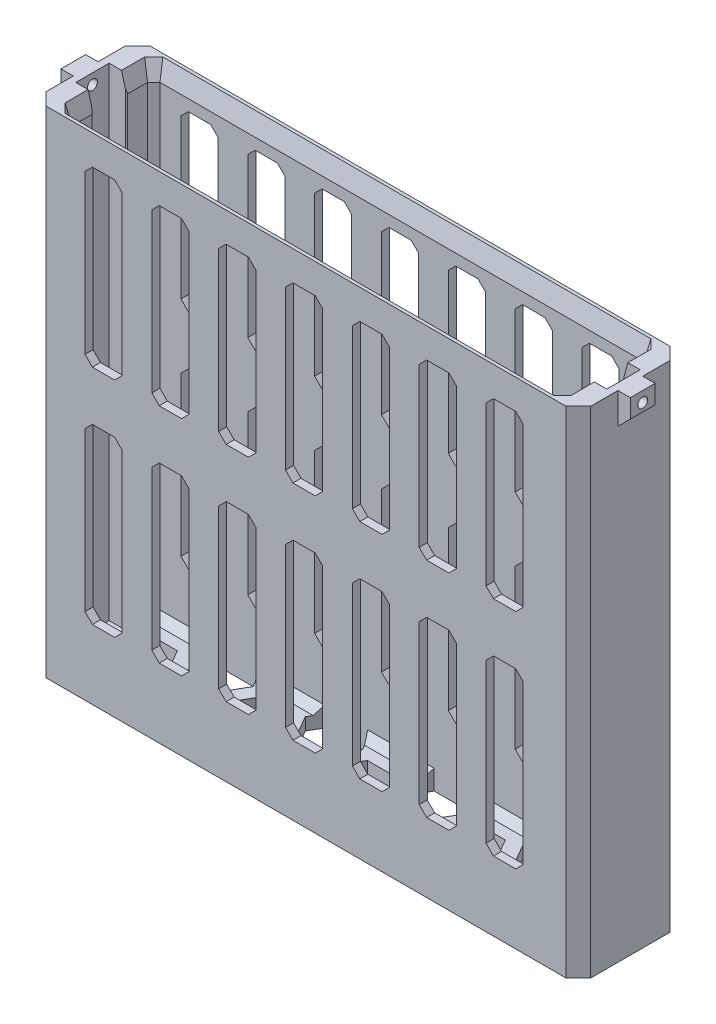
SolidWorks part; units mm, degrees
ref_plane "Front Plane" through (0, 0, 0) normal (0, 0, 1) x (1, 0, 0)
ref_plane "Top Plane" through (0, 0, 0) normal (0, 1, 0) x (1, 0, 0)
ref_plane "Right Plane" through (0, 0, 0) normal (1, 0, 0) x (0, 0, -1)
sketch "Sketch1" plane through (0, 0, 0) normal (0, 1, 0) x (1, 0, 0)
  line L0 (-100.25, -6.75) -> (-100.25, -15.25)
  line L1 (110, 21) -> (-110, 21)
  line L2 (110, 21) -> (110, -21)
  line L3 (110, -21) -> (-110, -21)
  line L4 (-110, 21) -> (-110, -21)
  line L5 (110, 21) -> (-110, -21) construction
  line L6 (110, -21) -> (-110, 21) construction
  line L7 (-97.75, 17.75) -> (97.75, 17.75)
  line L8 (-100.25, 15.25) -> (-100.25, 6.75)
  line L9 (-97.75, -17.75) -> (97.75, -17.75)
  line L10 (100.25, 15.25) -> (100.25, 6.75)
  line L11 (-100.25, 17.75) -> (100.25, -17.75) construction
  line L12 (-100.25, -17.75) -> (100.25, 17.75) construction
  line L13 (-107.25, 6.75) -> (-100.25, 6.75)
  line L14 (-107.25, 6.75) -> (-107.25, -6.75)
  line L15 (-107.25, -6.75) -> (-100.25, -6.75)
  line L17 (100.25, -6.75) -> (100.25, -15.25)
  line L18 (-100.25, 15.25) -> (-97.75, 17.75)
  line L19 (100.25, 6.75) -> (107.25, 6.75)
  line L21 (100.25, -6.75) -> (107.25, -6.75)
  line L22 (107.25, 6.75) -> (107.25, -6.75)
  line L23 (-100.25, -15.25) -> (-97.75, -17.75)
  line L24 (97.75, 17.75) -> (100.25, 15.25)
  line L25 (97.75, -17.75) -> (100.25, -15.25)
  point P0 (0, 0)
  point P5 (0, 0)
  point P11 (-100.25, 0)
  point P12 (-100.25, 0)
  point P17 (100.25, 0)
extrude "Boss-Extrude1" add sketch "Sketch1" along normal blind 200
chamfer "Chamfer1" distance 0.5 angle 45 4 edges at (100.25, 100, 6.75) (100.25, 100, -6.75) (-100.25, 100, 6.75) (-100.25, 100, -6.75)
chamfer "Chamfer2" distance 2 angle 75 10 edges at (100.25, 200, 11.25) (99, 200, 16.5) (0, 200, 17.75) (-99, 200, 16.5) (-100.25, 200, 11.25) (100.25, 200, -11.25) (99, 200, -16.5) (-100.25, 200, -11.25) (-99, 200, -16.5) (0, 200, -17.75) first distance on face at (0, 200, 0)
sketch "Sketch2" plane through (0, 0, 21) normal (0, 0, 1) x (1, 0, 0)
  line L0 (-89.2746, 185.0231) -> (-86.2746, 188.0231)
  line L1 (-86.2746, 188.0231) -> (-77.2746, 188.0231)
  line L2 (-89.2746, 185.0231) -> (-89.2746, 121.0231)
  line L3 (-86.2746, 118.0231) -> (-77.2746, 118.0231)
  line L4 (-74.2746, 185.0231) -> (-74.2746, 121.0231)
  line L5 (-77.2746, 188.0231) -> (-74.2746, 185.0231)
  line L6 (-89.2746, 121.0231) -> (-86.2746, 118.0231)
  line L7 (-77.2746, 118.0231) -> (-74.2746, 121.0231)
  point P0 (-89.2746, 188.0231)
  point P1 (-74.2746, 118.0231)
  point P2 (-89.2746, 118.0231)
  point P3 (-74.2746, 188.0231)
extrude "Cut-Extrude1" cut sketch "Sketch2" against normal up to surface (42 mm away) up to face at (0, 100, -21)
pattern_linear "LPattern1" count 7 spacing 27 along (1, 0, 0) count 2 spacing 90 along (0, -1, 0) of "Cut-Extrude1"
sketch "Sketch3" plane through (110, 0, 0) normal (1, 0, 0) x (0, 0, -1)
  line L0 (-21, 200) -> (21, 200) construction
  line L2 (-5, 200) -> (-5, 187.5)
  line L3 (-5, 187.5) -> (5, 187.5)
  line L4 (5, 200) -> (5, 187.5)
  line L5 (0, 200) -> (5, 187.5) construction
  line L6 (-5, 187.5) -> (0, 200) construction
  line L7 (-5, 200) -> (5, 200)
  point P0 (0, 200)
extrude "Boss-Extrude2" add sketch "Sketch3" along normal blind 5
sketch "Sketch4" plane through (115, 0, 0) normal (1, 0, 0) x (0, 0, -1)
  circle A0 centre (0, 195.7831) radius 2
extrude "Cut-Extrude2" cut sketch "Sketch4" against normal blind 10
chamfer "Chamfer3" distance 5 angle 45 1 edges at (115, 187.5, 0)
mirror "Mirror1" about plane through (0, 0, 0) normal (1, 0, 0) of "Boss-Extrude2", "Chamfer3", "Cut-Extrude2"
chamfer "Chamfer4" distance 5 angle 45 4 edges at (110, 100, 21) (110, 100, -21) (-110, 100, -21) (-110, 100, 21)
sketch "Sketch5" plane through (0, 0, 0) normal (0, -1, 0) x (1, 0, 0)
  line L13 (110, -16) -> (110, 16)
  line L14 (110, 16) -> (105, 21)
  line L15 (105, 21) -> (-105, 21)
  line L16 (-105, 21) -> (-110, 16)
  line L17 (-110, 16) -> (-110, -16)
  line L18 (-110, -16) -> (-105, -21)
  line L19 (-105, -21) -> (105, -21)
  line L20 (105, -21) -> (110, -16)
  line L21 (110, -16) -> (110, 16)
  line L22 (110, 16) -> (105, 21)
  line L23 (105, 21) -> (-105, 21)
  line L24 (-105, 21) -> (-110, 16)
  line L25 (-110, 16) -> (-110, -16)
  line L26 (-110, -16) -> (-105, -21)
  line L27 (-105, -21) -> (105, -21)
  line L28 (105, -21) -> (110, -16)
  point P0 (0, 0)
  dimension "D1" = 0
extrude "Boss-Extrude3" add sketch "Sketch5" against normal blind 5
sketch "Sketch7" plane through (0, 5, 0) normal (0, 1, 0) x (1, 0, 0)
  line L1 (-55.1053, 12.75) -> (-57.9921, 17.75)
  line L3 (-77.189, 0) -> (-82.9625, 10)
  line L4 (-82.9625, 10) -> (-94.5095, 10)
  line L5 (-94.5095, 10) -> (-100.283, 0)
  line L6 (-100.283, 0) -> (-94.5095, -10)
  line L7 (-94.5095, -10) -> (-82.9625, -10)
  line L8 (-82.9625, -10) -> (-77.189, 0)
  line L10 (-75.3126, 17.75) -> (-78.1993, 12.75)
  line L11 (-78.1993, 12.75) -> (-72.4258, 2.75)
  line L12 (-72.4258, 2.75) -> (-60.8788, 2.75)
  line L13 (-60.8788, 2.75) -> (-55.1053, 12.75)
  line L14 (-33.0217, 0) -> (-38.7952, 10)
  line L15 (-38.7952, 10) -> (-50.3422, 10)
  line L16 (-50.3422, 10) -> (-56.1157, 0)
  line L17 (-56.1157, 0) -> (-50.3422, -10)
  line L18 (-50.3422, -10) -> (-38.7952, -10)
  line L19 (-38.7952, -10) -> (-33.0217, 0)
  line L20 (-55.1053, -12.75) -> (-60.8788, -2.75)
  line L21 (-60.8788, -2.75) -> (-72.4258, -2.75)
  line L22 (-72.4258, -2.75) -> (-78.1993, -12.75)
  line L23 (-78.1993, -12.75) -> (-75.3126, -17.75)
  line L25 (-57.9921, -17.75) -> (-55.1053, -12.75)
  line L26 (-77.189, 0) -> (-55.1053, 12.75) construction
  line L28 (-75.3126, 17.75) -> (-57.9921, 17.75)
  line L29 (-57.9921, -17.75) -> (-75.3126, -17.75)
  line L30 (-97.75, 17.75) -> (97.75, 17.75) construction
  line L31 (-60.8788, 22.75) -> (-72.4258, 22.75) [skipped]
  line L32 (-72.4258, -22.75) -> (-60.8788, -22.75) [skipped]
  arc A0 (-97.3962, -5) -> (-80.0757, -5) centre (-88.736, 0) ccw construction
  arc A1 (-80.0757, 5) -> (-97.3962, 5) centre (-88.736, 0) ccw construction
  dimension "D1" = 2
  dimension "D3" = 25.5
  dimension "D2" = 2
extrude "Cut-Extrude3" cut sketch "Sketch7" against normal blind 5
pattern_linear "LPattern2" count 4 spacing 44.15 along (1, 0, 0) of "Cut-Extrude3"
chamfer "Chamfer5" distance 3 angle 45 10 edges at (86.104, 5, 17.75) (86.104, 5, -17.75) (43.7227, 5, -17.75) (43.7227, 5, 17.75) (-0.4273, 5, 17.75) (-44.5773, 5, 17.75) (-86.5313, 5, 17.75) (-86.5313, 5, -17.75) (-0.4273, 5, -17.75) (-44.5773, 5, -17.75)
